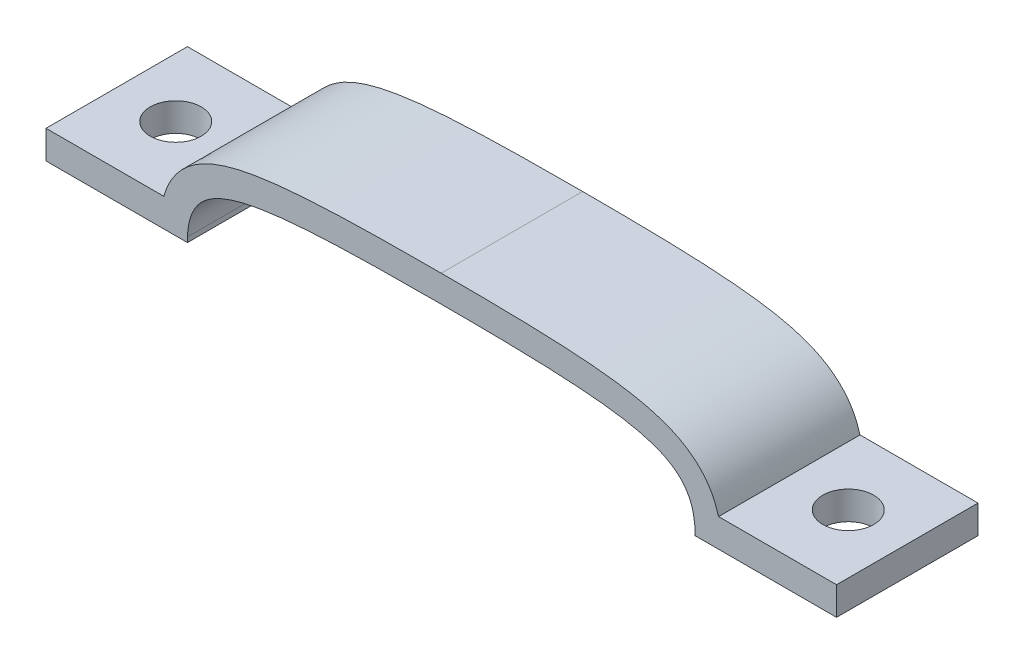
SolidWorks part; units mm, degrees
ref_plane "Front Plane" through (0, 0, 0) normal (0, 0, 1) x (1, 0, 0)
ref_plane "Top Plane" through (0, 0, 0) normal (0, 1, 0) x (1, 0, 0)
ref_plane "Right Plane" through (0, 0, 0) normal (1, 0, 0) x (0, 0, -1)
sketch "Sketch1" plane through (0, 0, 0) normal (0, 0, 1) x (1, 0, 0)
  line L1 (-24.3792, 158.0869) -> (-59.8719, 158.0869) construction
  line L2 (-59.8719, 158.4295) -> (-59.8719, 158.0869) construction
  line L3 (-60.0719, 158.4339) -> (-60.0719, 158.0869)
  line L4 (-60.0719, 158.0869) -> (-70.0719, 158.0869)
  line L5 (-24.1792, 158.0869) -> (-14.1792, 158.0869)
  line L8 (-70.0719, 158.0869) -> (-70.0719, 160.0869)
  line L9 (-22.5208, 160.0869) -> (-14.1792, 160.0869)
  line L10 (-70.0719, 160.0869) -> (-61.7376, 160.0869)
  line L11 (-14.1792, 158.0869) -> (-14.1792, 160.0869)
  spline S2 degree 3 poles (-24.3792, 158.0869) (-24.3792, 158.298) (-24.3948, 158.7203) (-24.4847, 159.3508) (-24.6697, 159.9591) (-25.0702, 160.7158) (-25.8681, 161.4447) (-27.0347, 161.9787) (-28.2637, 162.3243) (-29.5199, 162.5549) (-30.7848, 162.7171) (-32.0543, 162.832) (-33.324, 162.9151) (-34.5929, 162.9748) (-35.8594, 163.0175) (-37.1228, 163.0472) (-38.3821, 163.067) (-39.6369, 163.0793) (-40.8865, 163.0857) (-41.7157, 163.0869) (-42.1292, 163.0869) (-42.1292, 163.0869) knots 0.755163 0.755163 0.755163 0.755163 0.762814 0.770465 0.778117 0.785768 0.80107 0.816372 0.831675 0.846977 0.862279 0.877581 0.892884 0.908186 0.923488 0.938791 0.954093 0.969395 0.984697 1 1 1 1 1 construction
  spline S3 degree 3 poles (-42.1292, 163.0869) (-42.5602, 163.0869) (-43.4199, 163.0856) (-44.7033, 163.0787) (-45.9813, 163.0657) (-47.2546, 163.0449) (-48.5236, 163.0139) (-49.7889, 162.9698) (-51.0508, 162.9085) (-52.309, 162.8238) (-53.5636, 162.7072) (-54.8113, 162.5434) (-56.0496, 162.3114) (-57.2604, 161.9649) (-58.4099, 161.4309) (-59.1956, 160.7049) (-59.591, 159.953) (-59.7742, 159.3479) (-59.8475, 158.8331) (-59.8676, 158.5261) (-59.8719, 158.4295) knots 0.500001 0.500001 0.500001 0.500001 0.515949 0.531896 0.547844 0.563792 0.579739 0.595687 0.611634 0.627582 0.64353 0.659477 0.675425 0.691373 0.70732 0.723268 0.731242 0.739216 0.747189 0.750846 0.750846 0.750846 0.750846 construction
  spline S4 degree 1 poles (-24.1792, 158.0869) (-42.1292, 163.2869) knots 0 0 1 1 construction
  spline S5 degree 1 poles (-42.1292, 163.2869) (-60.0719, 158.4339) knots 0 0 1 1 construction
  spline S6 degree 3 poles (-24.1792, 158.0869) (-24.1792, 158.5234) (-24.2357, 159.392) (-24.7382, 160.6854) (-25.7619, 161.6186) (-26.9688, 162.168) (-28.2199, 162.5198) (-29.9133, 162.8302) (-32.0395, 163.0467) (-34.5867, 163.1831) (-37.1206, 163.2519) (-39.6401, 163.2822) (-41.2977, 163.2869) (-42.1292, 163.2869) knots 0.755163 0.755163 0.755163 0.755163 0.770465 0.785768 0.80107 0.816372 0.831675 0.846977 0.877582 0.908186 0.938791 0.969395 1 1 1 1
  spline S7 degree 3 poles (-42.1292, 163.2869) (-43.8105, 163.2869) (-46.3467, 163.2738) (-49.6708, 163.1825) (-52.1577, 163.0507) (-54.6335, 162.8009) (-56.6878, 162.3976) (-58.2655, 161.7469) (-59.3216, 160.9319) (-59.947, 159.7212) (-60.0527, 158.8638) (-60.0719, 158.4339) knots 0.500001 0.500001 0.500001 0.500001 0.562726 0.594089 0.625452 0.656814 0.688177 0.703858 0.719539 0.735221 0.750902 0.750902 0.750902 0.750902
  spline S8 degree 1 poles (-22.2792, 158.0869) (-42.1292, 165.1869) knots 0 0 1 1 construction
  spline S9 degree 1 poles (-42.1292, 165.1869) (-61.9698, 158.5229) knots 0 0 1 1 construction
  spline S10 degree 3 poles (-22.2792, 158.0869) (-22.2792, 158.3606) (-22.2962, 158.8364) (-22.3756, 159.4478) (-22.4761, 159.9283) (-22.5788, 160.3071) (-22.8045, 160.9303) (-23.2236, 161.7251) (-23.948, 162.5536) (-25.0053, 163.3701) (-26.3471, 163.9717) (-27.8025, 164.3752) (-29.2062, 164.6325) (-30.5609, 164.8055) (-32.3384, 164.9662) (-34.5145, 165.0817) (-37.0857, 165.1517) (-39.6279, 165.1822) (-41.293, 165.1869) (-42.1292, 165.1869) knots 0.755163 0.755163 0.755163 0.755163 0.762814 0.768956 0.770868 0.774694 0.778117 0.785768 0.793419 0.80107 0.816372 0.831675 0.846977 0.862279 0.877582 0.908186 0.938791 0.969395 1 1 1 1 only from (-22.5208, 160.0869) to (-42.1292, 165.1869)
  spline S11 degree 3 poles (-42.1292, 165.1869) (-42.9778, 165.1869) (-44.6782, 165.1819) (-47.2092, 165.1509) (-49.7419, 165.0816) (-52.291, 164.9459) (-54.4551, 164.7315) (-56.2551, 164.418) (-57.6652, 164.0494) (-59.1826, 163.4339) (-60.5111, 162.4374) (-61.3276, 161.228) (-61.6385, 160.4581) (-61.8063, 159.8398) (-61.9215, 159.2218) (-61.9573, 158.8041) (-61.9698, 158.5229) knots 0.500001 0.500001 0.500001 0.500001 0.531357 0.562712 0.594068 0.625424 0.656779 0.672457 0.688135 0.703813 0.71949 0.727329 0.734791 0.73871 0.743007 0.750846 0.750846 0.750846 0.750846 only from (-42.1292, 165.1869) to (-61.7376, 160.0869)
  point P10 (-24.1792, 160.0869)
  point P18 (-60.0719, 160.0869)
  dimension "D2" = 10
  dimension "D4" = 2
  dimension "D1" = 0.2
  dimension "D3" = 2.1
extrude "Boss-Extrude1" add sketch "Sketch1" along normal blind 10 contours L8 L4 L3 S7 S6 L5 L11 region at (-60.6353, 158.2604, 0)
sketch "Sketch2" plane through (0, 158.0869, 0) normal (0, -1, 0) x (-1, 0, 0)
  point P10 (18.35, -5)
  point P13 (65.9011, -5)
hole_wizard "M3 Clearance Hole1" positions "Sketch2" profile "Sketch3" hole size "M3" standard "ANSI Metric" end condition through all
sketch "Sketch3" plane through (-18.35, 158.0869, 5) normal (1, 0, 0) x (0, 0, -1)
  line L0 (0, 0) -> (0, 7.1)
  line L1 (0, 7.1) -> (1.8, 7.1)
  line L2 (1.8, 7.1) -> (1.8, 0)
  line L5 (1.8, 0) -> (0, 0)
  line L11 (0, -6.35) -> (0, 107.95) construction
  dimension "Thru Hole Dia." = 3.6
  dimension "Thru Hole Depth" = 7.1
